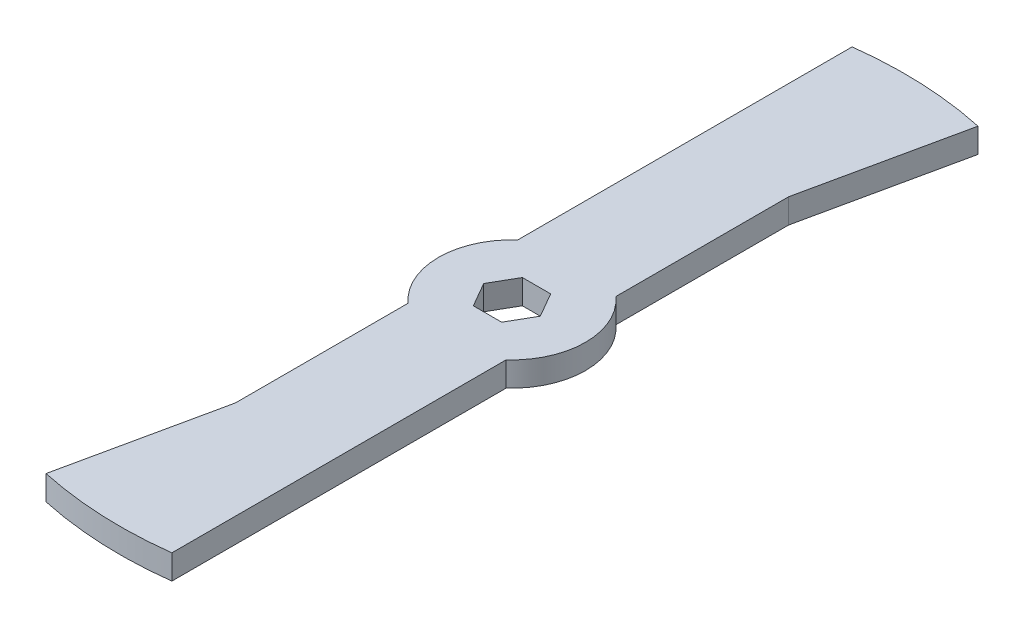
SolidWorks part; units mm, degrees
material "AISI 316 Stainless Steel Sheet (SS)"
ref_plane "Front Plane" through (0, 0, 0) normal (0, 0, 1) x (1, 0, 0)
ref_plane "Top Plane" through (0, 0, 0) normal (0, 1, 0) x (1, 0, 0)
ref_plane "Right Plane" through (0, 0, 0) normal (1, 0, 0) x (0, 0, -1)
sketch "Sketch1" plane through (0, 0, 0) normal (0, 1, 0) x (1, 0, 0)
  line L0 (0, 19.05) -> (0, 101.6) construction
  line L1 (-12.7, 100.8031) -> (-12.7, 14.199)
  line L2 (12.7, 14.199) -> (12.7, 58.973)
  line L3 (12.7, 58.973) -> (21.3895, 99.323)
  line L4 (12.7, -100.8031) -> (12.7, -14.199)
  line L5 (-12.7, -58.973) -> (-21.3895, -99.323)
  line L6 (-12.7, -14.199) -> (-12.7, -58.973)
  circle A1 centre (0, 0) radius 19.05 construction
  circle A2 centre (0, 0) radius 101.6 construction
  arc A3 (-12.7, 100.8031) -> (21.3895, 99.323) centre (0, 0) cw
  circle A4 centre (0, 0) radius 60.325 construction
  arc A5 (12.7, -100.8031) -> (-21.3895, -99.323) centre (0, 0) cw
  arc A6 (-12.7, 14.199) -> (-12.7, -14.199) centre (0, 0) ccw
  arc A7 (12.7, 14.199) -> (12.7, -14.199) centre (0, 0) cw
  point P9 (12.7, 14.199)
  point P15 (0, 60.325)
  point P23 (0, 0)
  dimension "D2" = 38.1
  dimension "D3" = 203.2
  dimension "D4" = 25.4
  dimension "D6" = 2
extrude "Boss-Extrude1" add sketch "Sketch1" along normal blind 6.35 contours A7 L2 L3 A3 L1 A6 L6 L5 A5 L4 region at (0, 0, 0)
sketch "Sketch3" plane through (0, 6.35, 0) normal (0, 1, 0) x (1, 0, 0)
  line L1 (7.3323, 0) -> (3.6662, 6.35)
  line L2 (3.6662, 6.35) -> (-3.6662, 6.35)
  line L3 (-3.6662, 6.35) -> (-7.3323, 0)
  line L4 (-7.3323, 0) -> (-3.6662, -6.35)
  line L5 (-3.6662, -6.35) -> (3.6662, -6.35)
  line L6 (3.6662, -6.35) -> (7.3323, 0)
  circle A0 centre (0, 0) radius 6.35 construction
  dimension "D1" = 12.7
extrude "Cut-Extrude2" cut sketch "Sketch3" against normal up to next
